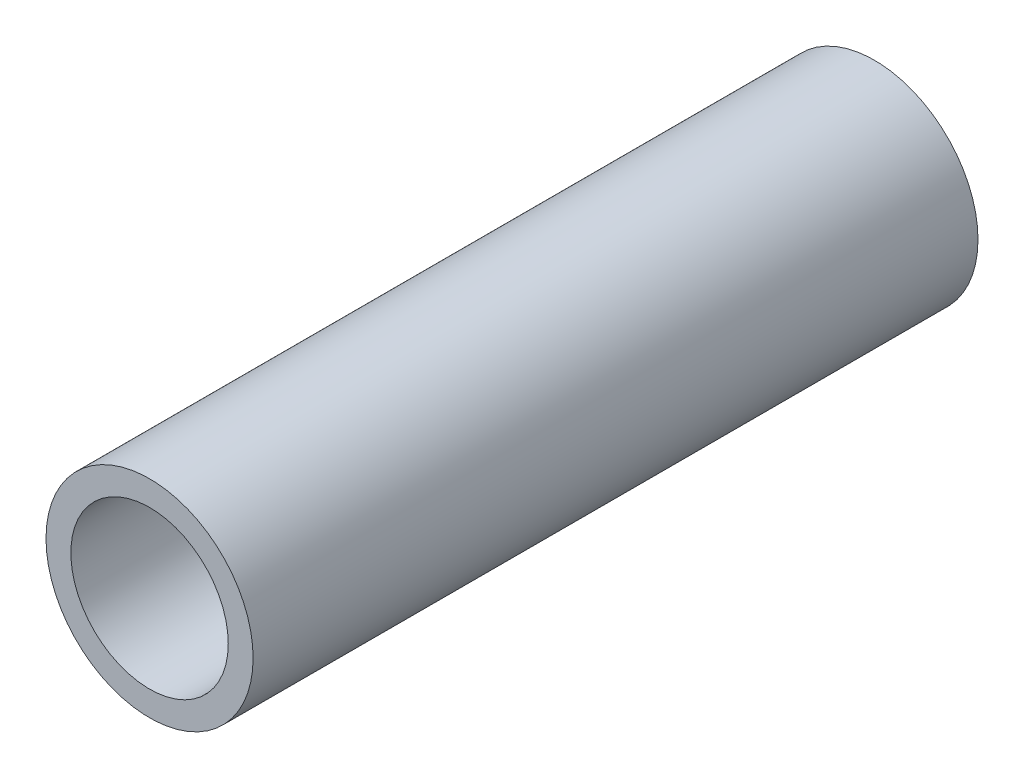
SolidWorks part; units mm, degrees
ref_plane "Front Plane" through (0, 0, 0) normal (0, 0, 1) x (1, 0, 0)
ref_plane "Top Plane" through (0, 0, 0) normal (0, 1, 0) x (1, 0, 0)
ref_plane "Right Plane" through (0, 0, 0) normal (1, 0, 0) x (0, 0, -1)
sketch "Sketch1" plane through (0, 0, 0) normal (0, 0, 1) x (1, 0, 0)
  circle A0 centre (0, 0) radius 6.35
  circle A1 centre (0, 0) radius 4.826
  dimension "D1" = 1.524
  dimension "OD" = 12.7
extrude "Boss-Extrude1" add sketch "Sketch1" along normal mid plane 44.45
ref_plane "Contact Plane 1" through (0, 0, 22.225) normal (0, 0, 1) x (1, 0, 0)
ref_axis "Center Axis 1" through (0, 0, 22.225) along (0, 0, -1)
